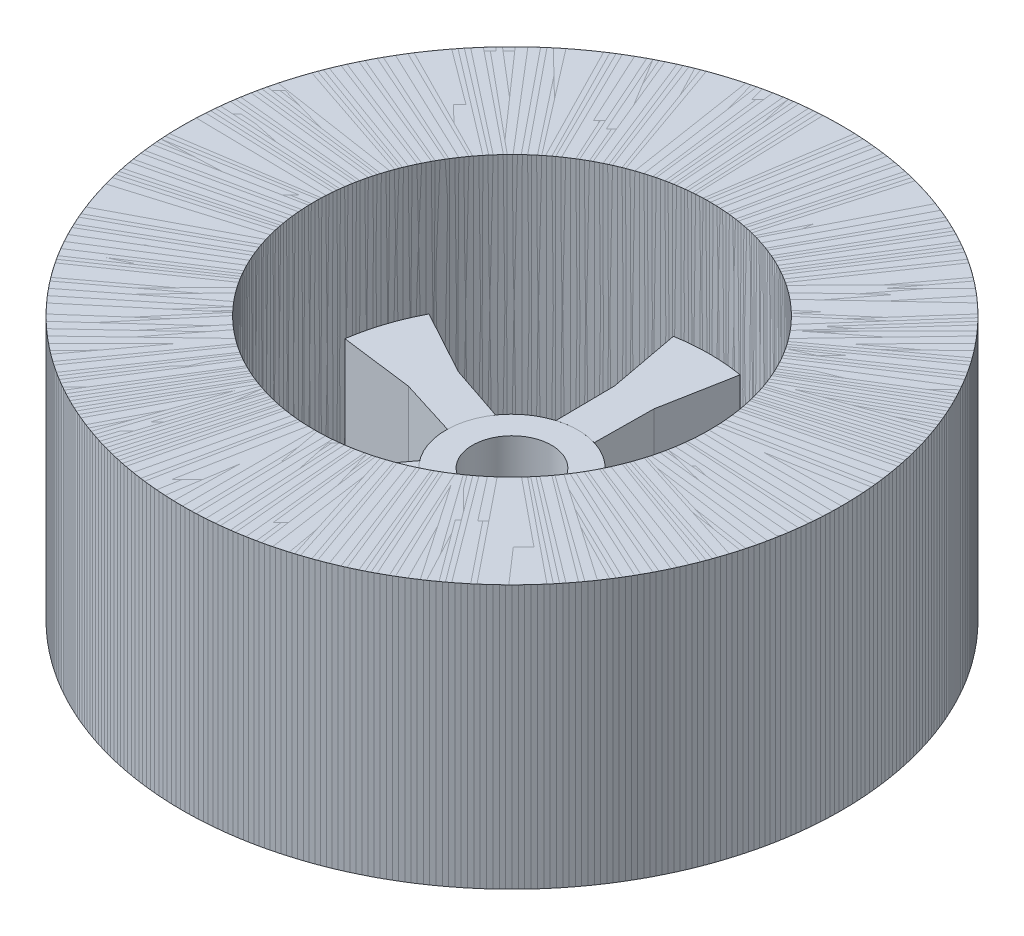
SolidWorks part; units mm, degrees
ref_plane "Front Plane" through (0, 0, 0) normal (0, 0, 1) x (1, 0, 0)
ref_plane "Top Plane" through (0, 0, 0) normal (0, 1, 0) x (1, 0, 0)
ref_plane "Right Plane" through (0, 0, 0) normal (1, 0, 0) x (0, 0, -1)
sketch "Sketch1" plane through (0, 0, 0) normal (0, 1, 0) x (1, 0, 0)
  line L2 (-2.5316, 14.7848) -> (-1.5, 9.2848)
  line L4 (1.451, 4.7848) -> (1.5, 9.2848)
  line L5 (1.5, 9.2848) -> (2.5316, 14.7848)
  line L6 (-1.5, 9.2848) -> (-1.451, 4.7848)
  line L7 (0, -55) -> (0, 55) construction
  circle A0 centre (0, 0) radius 15
  circle A1 centre (0, 0) radius 25
  arc A2 (-2.5316, 14.7848) -> (2.5316, 14.7848) centre (0, 0) cw
  circle A3 centre (0, 0) radius 5
  arc A4 (-1.451, 4.7848) -> (1.451, 4.7848) centre (0, 0) cw
  circle A5 centre (0, 0) radius 3
  dimension "D1" = 30
  dimension "D2" = 50
  dimension "D3" = 6
  dimension "D4" = 10
  dimension "D5" = 5
  dimension "D6" = 5.5
  dimension "D7" = 4.5
  dimension "D8" = 170
  dimension "D9" = 170
  dimension "D10" = 1.5
  dimension "D11" = 1.5
extrude "Boss-Extrude1" add sketch "Sketch1" along normal blind 20 contours A1 A0 region at (-24.2929, 0, 0)
extrude "Boss-Extrude3" add sketch "Sketch1<4>" along normal blind 10 contours A3 L4 L5 A0 L2 L6 region at (0, 0, -10.4697)
sketch "Sketch1<4>" plane through (0, 0, 0) normal (0, 1, 0) x (1, 0, 0) same geometry as "Sketch1"
extrude "Boss-Extrude2" add sketch "Sketch1<3>" along normal blind 10 separate body contours A4 L6 A3 A5 region at (0, 0, -4.8586)
sketch "Sketch1<3>" plane through (0, 0, 0) normal (0, 1, 0) x (1, 0, 0) same geometry as "Sketch1"
pattern_circular "CirPattern7" count 5 over 360 about axis through (0, 0, 0) along (0, 1, 0) of bodies 111
ref_plane "Plane1" through (0, 80, 0) normal (0, 1, 0) x (1, 0, 0)
